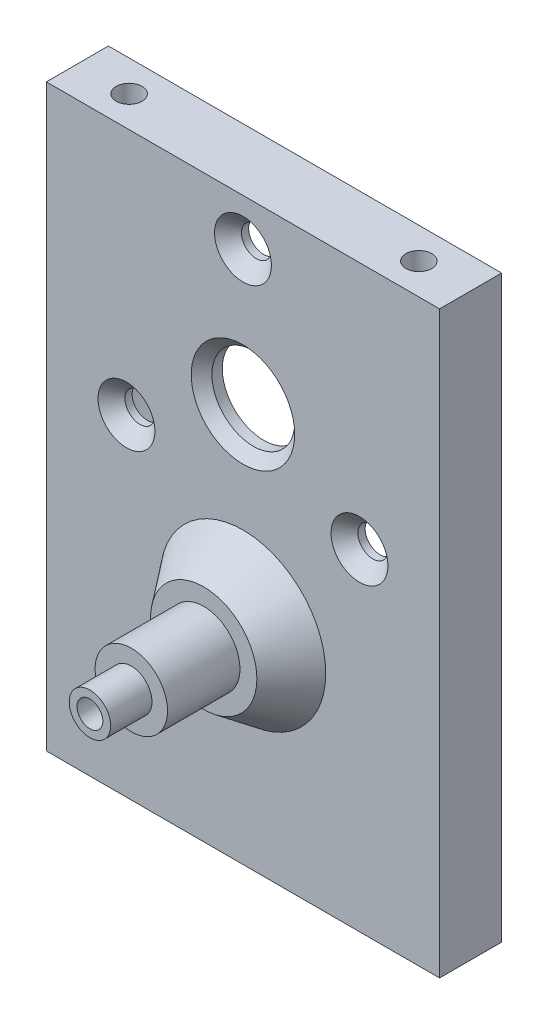
SolidWorks part; units mm, degrees
ref_plane "Plano frontal" through (0, 0, 0) normal (0, 0, 1) x (1, 0, 0)
ref_plane "Plano superior" through (0, 0, 0) normal (0, 1, 0) x (1, 0, 0)
ref_plane "Plano direito" through (0, 0, 0) normal (1, 0, 0) x (0, 0, -1)
sketch "Esboço1" plane through (0, 0, 0) normal (0, 0, 1) x (1, 0, 0)
  line L0 (-19, 0) -> (19, 0)
  line L1 (19, 0) -> (19, 56)
  line L2 (19, 56) -> (-19, 56)
  line L4 (-19, 56) -> (-19, 0)
  circle A1 centre (0, 20) radius 4
  point P9 (-19, 0)
  dimension "D7" = 8
  dimension "D2" = 38
  dimension "D4" = 56
  dimension "D8" = 20
  dimension "D11" = 38
extrude "Ressalto-extrusão1" add sketch "Esboço1" along normal blind 6
sketch "Esboço6" plane through (0, 0, 0) normal (0, 0, -1) x (-1, 0, 0)
  line L1 (0, 38.5) -> (-19, 38.5) construction
  line L3 (-19, 0) -> (-19, 56) construction
  line L5 (0, 38.5) -> (0, 0) construction
  line L6 (19, 0) -> (-19, 0) construction
  circle A0 centre (0, 38.5) radius 16.54
  circle A1 centre (0, 20) radius 4 construction
  circle A2 centre (0, 20) radius 4 construction
  dimension "D1" = 33.08
  dimension "D2" = 18.5
  dimension "D3" = 19
extrude "Corte-extrusão5" cut sketch "Esboço6" against normal blind 4
sketch "Esboço7" plane through (0, 0, 4) normal (0, 0, -1) x (-1, 0, 0)
  line L0 (0, 51.5) -> (0, 38.5) construction
  line L1 (0, 38.5) -> (-11.2583, 32) construction
  circle A0 centre (0, 38.5) radius 4
  circle A1 centre (11.2583, 32) radius 1.25
  circle A2 centre (-11.2583, 32) radius 1.25
  circle A3 centre (0, 38.5) radius 16.54 construction
  circle A4 centre (0, 51.5) radius 1.25
  dimension "D1" = 8
  dimension "D2" = 2.5
  dimension "D6" = 13
  dimension "D3" = 13
  dimension "D5" = 120
  dimension "D4" = 3
extrude "Corte-extrusão6" cut sketch "Esboço7" against normal through all
hole_wizard "Escareado para parafuso de máquina com cabeça chata de M2.51" positions "Esboço9" profile "Esboço10" countersink size "M2.5" standard "Métrico Ansi"
sketch "Esboço9" plane through (0, 0, 6) normal (0, 0, 1) x (1, 0, 0)
  point P0 (0, 51.5)
  point P1 (11.2583, 32)
  point P4 (-11.2583, 32)
sketch "Esboço10" plane through (0, 51.5, 6) normal (1, 0, 0) x (0, -1, 0)
  line L0 (0, 0) -> (0, 2.8702)
  line L1 (0, 2.8702) -> (1.45, 1.999)
  line L2 (1.45, 1.999) -> (1.45, 1.3)
  line L3 (1.45, 1.3) -> (2.75, 0)
  line L5 (2.75, 0) -> (0, 0)
  line L6 (-1.45, 1.3) -> (-2.75, 0) construction
  line L10 (0, 2.8702) -> (-1.45, 1.999) construction
  line L11 (0, -6.35) -> (0, 107.95) construction
  dimension "Hole Dia." = 2.9
  dimension "Hole Depth" = 1.999
  dimension "Near C'Sink Dia." = 5.5
  dimension "Near C'Sink Angle" = 90
  dimension "Drill Angle" = 118
sketch "Esboço15" plane through (0, 0, 0) normal (0, 0, -1) x (-1, 0, 0)
  arc A0 (-3.2806, 22.2886) -> (3.2806, 22.2886) centre (0, 20) ccw construction
  arc A1 (-3.2806, 22.2886) -> (3.2806, 22.2886) centre (0, 20) ccw
  arc A2 (-3.2806, 22.2886) -> (3.2806, 22.2886) centre (0, 38.5) ccw
  arc A3 (3.2806, 22.2886) -> (-3.2806, 22.2886) centre (0, 38.5) ccw construction
extrude "Ressalto-extrusão2" add sketch "Esboço15" against normal up to surface (4 mm away) up to face at (-12.7083, 32, 4)
sketch "Esboço16" plane through (0, 0, 4) normal (0, 0, 1) x (1, 0, 0)
  arc A0 (-3.2806, 22.2886) -> (3.2806, 22.2886) centre (0, 20) ccw construction
  arc A1 (3.2806, 22.2886) -> (-3.2806, 22.2886) centre (0, 20) ccw construction
  arc A2 (-3.2806, 22.2886) -> (3.2806, 22.2886) centre (0, 20) ccw
  arc A3 (3.2806, 22.2886) -> (-3.2806, 22.2886) centre (0, 20) ccw
extrude "Ressalto-extrusão3" add sketch "Esboço16" along normal blind 5.79
sketch "Esboço17" plane through (0, 0, 9.79) normal (0, 0, 1) x (1, 0, 0)
  circle A0 centre (0, 20) radius 3.5
  dimension "D1" = 7
extrude "Ressalto-extrusão4" add sketch "Esboço17" along normal blind 7
sketch "Esboço18" plane through (0, 0, 16.79) normal (0, 0, 1) x (1, 0, 0)
  circle A0 centre (0, 20) radius 2
  dimension "D1" = 4
extrude "Ressalto-extrusão5" add sketch "Esboço18" along normal blind 4
chamfer "Chanfro1" distance 4 distance2 5.29 1 edges at (4, 20, 6) first distance on face at (2.75, 51.5, 6)
hole_wizard "Furo roscado de M3x0.51" positions "Esboço22" profile "Esboço21" tap size "M3x0.5" standard "Ansi Metric"
sketch "Esboço22" plane through (0, 0, 20.79) normal (0, 0, 1) x (1, 0, 0)
  point P0 (0, 20)
sketch "Esboço21" plane through (0, 20, 20.79) normal (1, 0, 0) x (0, -1, 0)
  line L0 (0, 0) -> (0, 10.7511)
  line L1 (0, 10.7511) -> (1.25, 10)
  line L2 (1.25, 10) -> (1.25, 0)
  line L5 (1.25, 0) -> (0, 0)
  line L10 (0, 10.7511) -> (-1.25, 10) construction
  line L11 (0, -6.35) -> (0, 107.95) construction
  dimension "Tap Drill Dia." = 2.5
  dimension "Tap Drill Depth" = 10
  dimension "Drill Angle" = 118
cosmetic thread "Rosca de furo1" parameters "D1"=6, "D2"=3
sketch "Esboço29" plane through (0, 0, 0) normal (0, -1, 0) x (1, 0, 0)
  line L0 (-19, 3) -> (19, 3) construction
  line L1 (-19, 6) -> (-19, 0) construction
  line L2 (19, 6) -> (19, 0) construction
  point P6 (-12, 3)
  point P7 (0, 3)
  point P8 (12, 3)
  dimension "D1" = 12
  dimension "D2" = 12
sketch "Esboço30" plane through (0, 56, 0) normal (0, 1, 0) x (1, 0, 0)
  line L0 (19, -3) -> (-19, -3) construction
  line L1 (19, -6) -> (19, 0) construction
  line L2 (-19, -6) -> (-19, 0) construction
  point P6 (14, -3)
  point P7 (-14, -3)
  dimension "D1" = 5
  dimension "D2" = 5
hole_wizard "Furo roscado de M3x0.52" positions "Esboço32" profile "Esboço31" tap size "M3x0.5" standard "Ansi Metric"
sketch "Esboço32" plane through (0, 0, 0) normal (0, -1, 0) x (-1, 0, 0)
  point P0 (12, -3)
  point P3 (0, -3)
  point P6 (-12, -3)
sketch "Esboço31" plane through (-12, 0, 3) normal (1, 0, 0) x (0, 0, -1)
  line L0 (0, 0) -> (0, 9.2511)
  line L1 (0, 9.2511) -> (1.25, 8.5)
  line L2 (1.25, 8.5) -> (1.25, 0)
  line L5 (1.25, 0) -> (0, 0)
  line L10 (0, 9.2511) -> (-1.25, 8.5) construction
  line L11 (0, -6.35) -> (0, 107.95) construction
  dimension "Tap Drill Dia." = 2.5
  dimension "Tap Drill Depth" = 8.5
  dimension "Drill Angle" = 118
cosmetic thread "Rosca de furo2" parameters "D1"=6, "D2"=3
cosmetic thread "Rosca de furo3" parameters "D1"=6, "D2"=3
cosmetic thread "Rosca de furo4" parameters "D1"=6, "D2"=3
hole_wizard "Furo roscado de M3x0.53" positions "Esboço34" profile "Esboço33" tap size "M3x0.5" standard "Ansi Metric"
sketch "Esboço34" plane through (0, 56, 0) normal (0, 1, 0) x (1, 0, 0)
  point P0 (-14, -3)
  point P3 (14, -3)
sketch "Esboço33" plane through (-14, 56, 3) normal (1, 0, 0) x (0, 0, 1)
  line L0 (0, 0) -> (0, 6.7511)
  line L1 (0, 6.7511) -> (1.25, 6)
  line L2 (1.25, 6) -> (1.25, 0)
  line L5 (1.25, 0) -> (0, 0)
  line L10 (0, 6.7511) -> (-1.25, 6) construction
  line L11 (0, -6.35) -> (0, 107.95) construction
  dimension "Tap Drill Dia." = 2.5
  dimension "Tap Drill Depth" = 6
  dimension "Drill Angle" = 118
cosmetic thread "Rosca de furo5" parameters "D1"=6, "D2"=3
cosmetic thread "Rosca de furo6" parameters "D1"=6, "D2"=3
chamfer "Chanfro2" distance 1 angle 45 1 edges at (-4, 38.5, 6)
